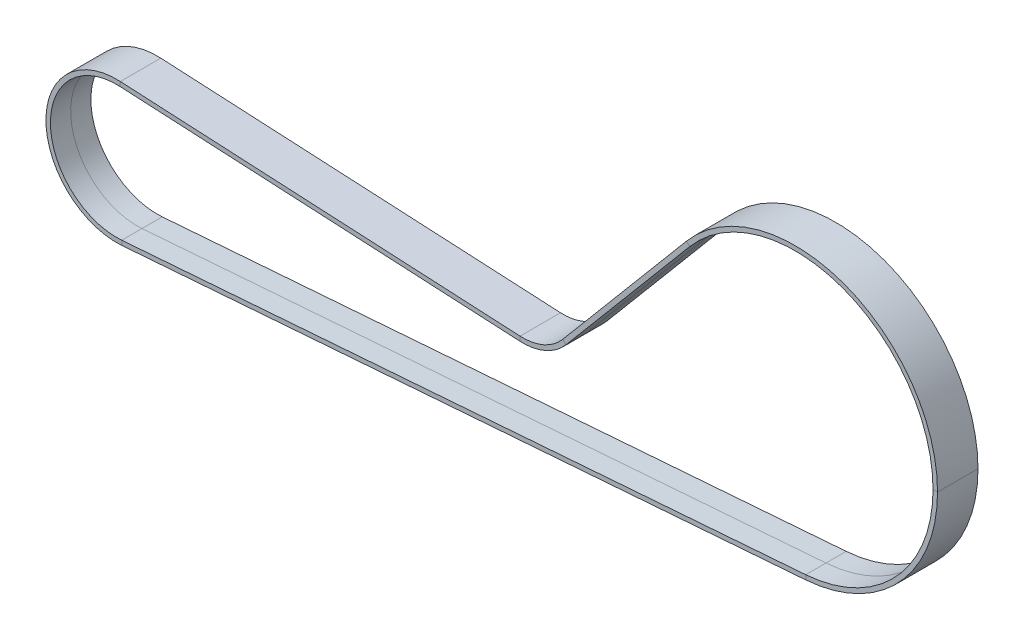
SolidWorks part; units mm, degrees
ref_plane "Front Plane" through (0, 0, 0) normal (0, 0, 1) x (1, 0, 0)
ref_plane "Top Plane" through (0, 0, 0) normal (0, 1, 0) x (1, 0, 0)
ref_plane "Right Plane" through (0, 0, 0) normal (1, 0, 0) x (0, 0, -1)
sketch "Sketch2" plane through (0, 0, 0) normal (0, 0, 1) x (1, 0, 0)
  line L0 (0, 0) -> (1, 0) construction
  line L1 (0, 0) -> (0, 1) construction
  line L2 (4.0693, -32.1661) -> (-148.0309, -43.7974)
  line L3 (-148.4344, -11.1767) -> (-59.5449, -15.7663)
  line L4 (-50.5644, -11.8672) -> (-23.0644, 20.7823)
  arc A0 (-23.0644, 20.7823) -> (4.0693, -32.1661) centre (1.6096, 0) cw
  arc A1 (-148.0309, -43.7974) -> (-148.4344, -11.1767) centre (-149.2772, -27.5) cw
  arc A2 (-59.5449, -15.7663) -> (-50.5644, -11.8672) centre (-58.9777, -4.7809) ccw
sketch "Sketch3" plane through (0, 0, 0) normal (0, 1, 0) x (1, 0, 0)
  line L0 (32.26, 0) -> (32.26, -4.5)
  line L1 (-23.0644, 0) -> (33.8696, 0) construction
  line L2 (32.26, -4.5) -> (33.26, -4.5)
  line L3 (33.26, -4.5) -> (33.26, 4.5)
  line L4 (33.26, 4.5) -> (32.26, 4.5)
  line L5 (32.26, 4.5) -> (32.26, 0)
  point P8 (33.26, 0)
  dimension "D1" = 1
  dimension "D2" = 9
  dimension "D3" = 32.26
sweep "Sweep1" add profiles "Sketch3" path "Sketch2"
